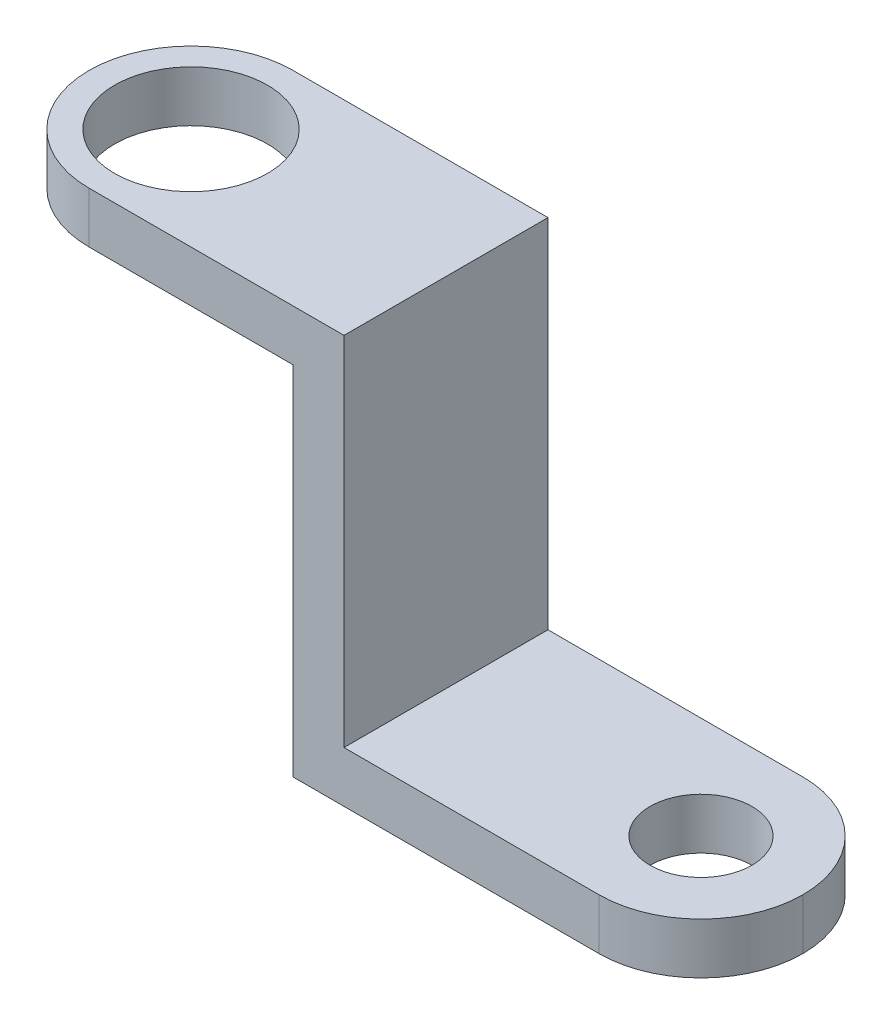
SolidWorks part; units mm, degrees
material "Brass"
ref_plane "Front" through (0, 0, 0) normal (0, 0, 1) x (1, 0, 0)
ref_plane "Top" through (0, 0, 0) normal (0, 1, 0) x (1, 0, 0)
ref_plane "Right" through (0, 0, 0) normal (1, 0, 0) x (0, 0, -1)
sketch "Sketch1" plane through (0, 0, 0) normal (0, 0, 1) x (1, 0, 0)
  line L0 (-38.1, 44.45) -> (0, 44.45)
  line L1 (0, 44.45) -> (0, 0)
  line L2 (0, 0) -> (50.8, 0)
  line L3 (50.8, 0) -> (50.8, 6.35)
  line L4 (50.8, 6.35) -> (6.35, 6.35)
  line L5 (6.35, 6.35) -> (6.35, 50.8)
  line L6 (6.35, 50.8) -> (-38.1, 50.8)
  line L7 (-38.1, 50.8) -> (-38.1, 44.45)
  dimension "D1" = 6.35
  dimension "D2" = 44.45
  dimension "D3" = 88.9
  dimension "D4" = 44.45
  dimension "D5" = 6.35
extrude "Boss-Extrude1" add sketch "Sketch1" along normal blind 25.4
fillet "Fillet1" radius 12.7 4 edges at (50.8, 3.175, 0) (-38.1, 47.625, 0) (50.8, 3.175, 25.4) (-38.1, 47.625, 25.4)
hole_wizard "3/4 (0.75) Diameter Hole1" positions "Sketch2" profile "Sketch3" hole size "3/4" standard "ANSI Inch" end condition through all
sketch "Sketch2" plane through (0, 50.8, 0) normal (0, 1, 0) x (1, 0, 0)
  point P0 (-25.4, -12.7)
  point P10 (0, 0)
sketch "Sketch3" plane through (-25.4, 50.8, 12.7) normal (1, 0, 0) x (0, 0, 1)
  line L0 (0, 0) -> (0, 50.8)
  line L1 (0, 50.8) -> (9.525, 50.8)
  line L2 (9.525, 50.8) -> (9.525, 0)
  line L5 (9.525, 0) -> (0, 0)
  line L11 (0, -6.35) -> (0, 107.95) construction
  dimension "Thru Hole Dia." = 19.05
  dimension "Thru Hole Depth" = 50.8
hole_wizard "1/2 (0.5) Diameter Hole2" positions "Sketch4" profile "Sketch5" hole size "1/2" standard "ANSI Inch" end condition through all
sketch "Sketch4" plane through (0, 6.35, 0) normal (0, 1, 0) x (1, 0, 0)
  point P0 (38.1, -12.7)
sketch "Sketch5" plane through (38.1, 6.35, 12.7) normal (1, 0, 0) x (0, 0, 1)
  line L0 (0, 0) -> (0, 6.35)
  line L1 (0, 6.35) -> (6.35, 6.35)
  line L2 (6.35, 6.35) -> (6.35, 0)
  line L5 (6.35, 0) -> (0, 0)
  line L11 (0, -6.35) -> (0, 107.95) construction
  dimension "Thru Hole Dia." = 12.7
  dimension "Thru Hole Depth" = 6.35
